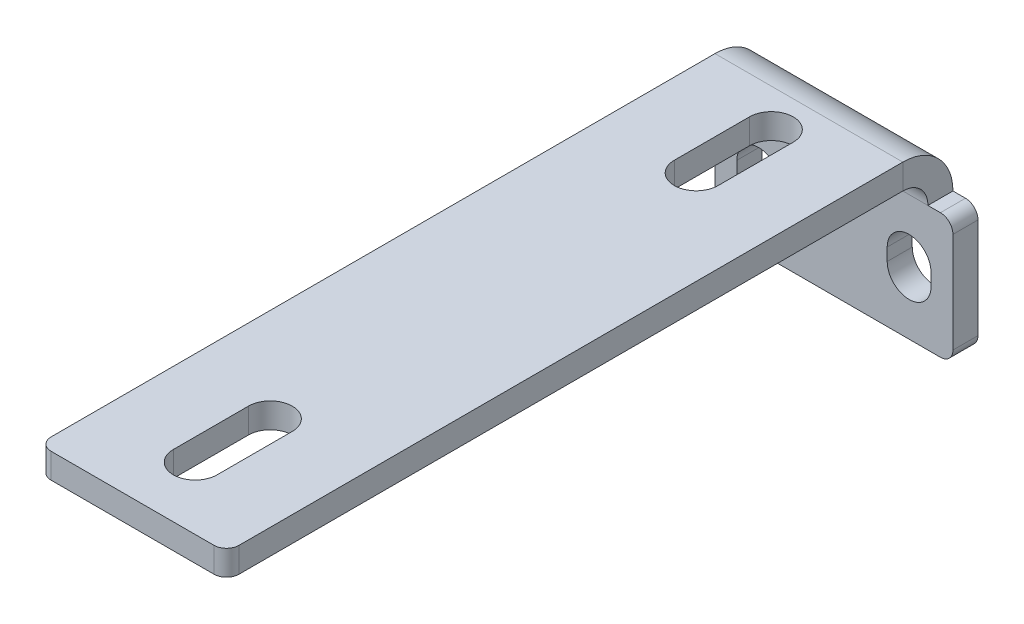
SolidWorks part; units mm, degrees
note: The reader was unsure of these and kept them because the rebuilt part matched: flange length of "Brida de arista1".
material "acero"
ref_plane "Alzado" through (0, 0, 0) normal (0, 0, 1) x (1, 0, 0)
ref_plane "Planta" through (0, 0, 0) normal (0, 1, 0) x (1, 0, 0)
ref_plane "Vista lateral" through (0, 0, 0) normal (1, 0, 0) x (0, 0, -1)
sketch "Croquis1" plane through (0, 0, 0) normal (0, 0, 1) x (1, 0, 0)
  line L0 (0, -5) -> (9.5, -5) construction
  line L1 (0, 0) -> (19, 0)
  line L2 (0, 0) -> (0, -10)
  line L3 (0, -10) -> (19, -10)
  line L4 (19, 0) -> (19, -10)
  line L5 (9.5, 0) -> (9.5, -10) construction
  line L6 (3.5, -4.5) -> (3.5, -5.5) construction
  line L7 (5.25, -4.5) -> (5.25, -5.5)
  line L8 (1.75, -4.5) -> (1.75, -5.5)
  line L9 (15.5, -4.5) -> (15.5, -5.5) construction
  line L10 (17.25, -4.5) -> (17.25, -5.5)
  line L11 (13.75, -4.5) -> (13.75, -5.5)
  circle A0 centre (3.5, -5) radius 1.75 construction
  circle A1 centre (15.5, -5) radius 1.75 construction
  arc A2 (5.25, -4.5) -> (1.75, -4.5) centre (3.5, -4.5) ccw
  arc A3 (1.75, -5.5) -> (5.25, -5.5) centre (3.5, -5.5) ccw
  arc A4 (17.25, -4.5) -> (13.75, -4.5) centre (15.5, -4.5) ccw
  arc A5 (13.75, -5.5) -> (17.25, -5.5) centre (15.5, -5.5) ccw
  point P15 (3.5, -5)
  point P22 (15.5, -5)
  dimension "D1" = 3.5
  dimension "D2" = 3.5
  dimension "D3" = 12
  dimension "D4" = 5
  dimension "D6" = 1
  dimension "D5" = 1.75
base flange "Brida base1" sketch "Croquis1" thickness 2 reverse thickness direction no parameters "D1"=1
edge flange "Brida de arista1" sketch "Croquis8" flange angle 90 flange length 56 flange position bend outside bend radius 2 thickness 2 relief rectangular parameters "D6"=10
sketch "Croquis8" plane through (0, 0, 0) normal (0, 1, 0) x (-1, 0, 0)
  line L3 (-17, 56) -> (-2, 56)
  line L4 (-2, 0) -> (-2, 56)
  line L5 (-19, 0) -> (0, 0) construction
  line L6 (-9.5, 0) -> (-9.5, 39.9038) construction
  line L7 (-17, 0) -> (-2, 0)
  line L9 (-17, 0) -> (-17, 56)
  line L10 (-17, 0) -> (-9.5, 0) construction
  line L11 (-9.5, 0) -> (-2, 0) construction
  dimension "D1" = 15
  dimension "D2" = 56
bend "Pliegue de arista1" bend radius 2 bend angle 90 parameters "D5"=1
sketch "Croquis9" plane through (0, 4, 0) normal (0, 1, 0) x (1, 0, 0)
  line L0 (9.5, -11) -> (9.5, -5) construction
  line L1 (7.75, -11) -> (7.75, -5)
  line L2 (11.25, -11) -> (11.25, -5)
  line L3 (9.5, -31) -> (9.5, -25) construction
  line L4 (7.75, -31) -> (7.75, -25) construction
  line L5 (17, -2) -> (2, -2) construction
  line L6 (11.25, -31) -> (11.25, -25) construction
  line L7 (9.5, -51) -> (9.5, -45) construction
  line L8 (7.75, -51) -> (7.75, -45)
  line L9 (9.5, -2) -> (9.5, -5) construction
  line L10 (11.25, -51) -> (11.25, -45)
  arc A0 (7.75, -31) -> (11.25, -31) centre (9.5, -31) ccw construction
  arc A1 (11.25, -25) -> (7.75, -25) centre (9.5, -25) ccw construction
  arc A2 (7.75, -11) -> (11.25, -11) centre (9.5, -11) ccw
  arc A3 (11.25, -5) -> (7.75, -5) centre (9.5, -5) ccw
  arc A4 (7.75, -51) -> (11.25, -51) centre (9.5, -51) ccw
  arc A5 (11.25, -45) -> (7.75, -45) centre (9.5, -45) ccw
  point P6 (9.5, -28)
  point P10 (9.5, -8)
  point P22 (9.5, -48)
  dimension "D1" = 6
  dimension "D3" = 40
  dimension "D5" = 1.75
  dimension "D2" = 3
  dimension "D4" = 6
extrude "Cortar-Extruir1" cut sketch "Croquis9" against normal up to next normal cut yes
fillet "Redondeo1" radius 1 6 edges at (19, -10, -1) (0, -10, -1) (19, 0, -1) (0, 0, -1) (17, 3, 56) (2, 3, 56)
sketch "Líneas de pliegue1" [suppressed] plane through (0, 0, 0) normal (0, 1, 0) x (1, 0, 0)
sketch "Cuadro delimitador1" [suppressed] plane through (0, 0, 0) normal (0, 1, 0) x (1, 0, 0)
sheet metal parameters "Chapa metálica4" thickness 2 parameters "D1"=1
flat pattern "Chapa desplegada4" [suppressed]
sketch "Líneas de pliegue2" plane through (0, 0, 0) normal (0, 1, 0) x (1, 0, 0)
sketch "Cuadro delimitador2" [suppressed] plane through (0, 0, 0) normal (0, 1, 0) x (1, 0, 0)
sheet metal parameters "Chapa metálica5" thickness 2 parameters "D1"=1
flat pattern "Chapa desplegada4" [suppressed]
sketch "Líneas de pliegue2" plane through (0, 0, 0) normal (0, 1, 0) x (1, 0, 0)
sketch "Cuadro delimitador2" [suppressed] plane through (0, 0, 0) normal (0, 1, 0) x (1, 0, 0)
bend of the flat pattern "Aplanar-<Pliegue de arista1>1"
sheet metal parameters "Chapa metálica6" thickness 2 parameters "D1"=1
flat pattern "Chapa desplegada4"
sketch "Líneas de pliegue2" plane through (0, 0, 0) normal (0, 0, 1) x (1, 0, 0)
  line L0 (25.7875, 1.9635) -> (0.2125, 1.9635) construction
  line L1 (25.7875, 1.9635) -> (0.2125, 1.9635) construction
sketch3d "Cuadro delimitador2" [suppressed]
  line L0 (26, -10, 0) -> (26, 55.627, 0) construction
  line L1 (0, -10, 0) -> (0, 55.627, 0) construction
  line L2 (26, -10, 0) -> (0, -10, 0) construction
  line L3 (26, 55.627, 0) -> (0, 55.627, 0) construction
bend of the flat pattern "Aplanar-<Pliegue de arista1>1"
